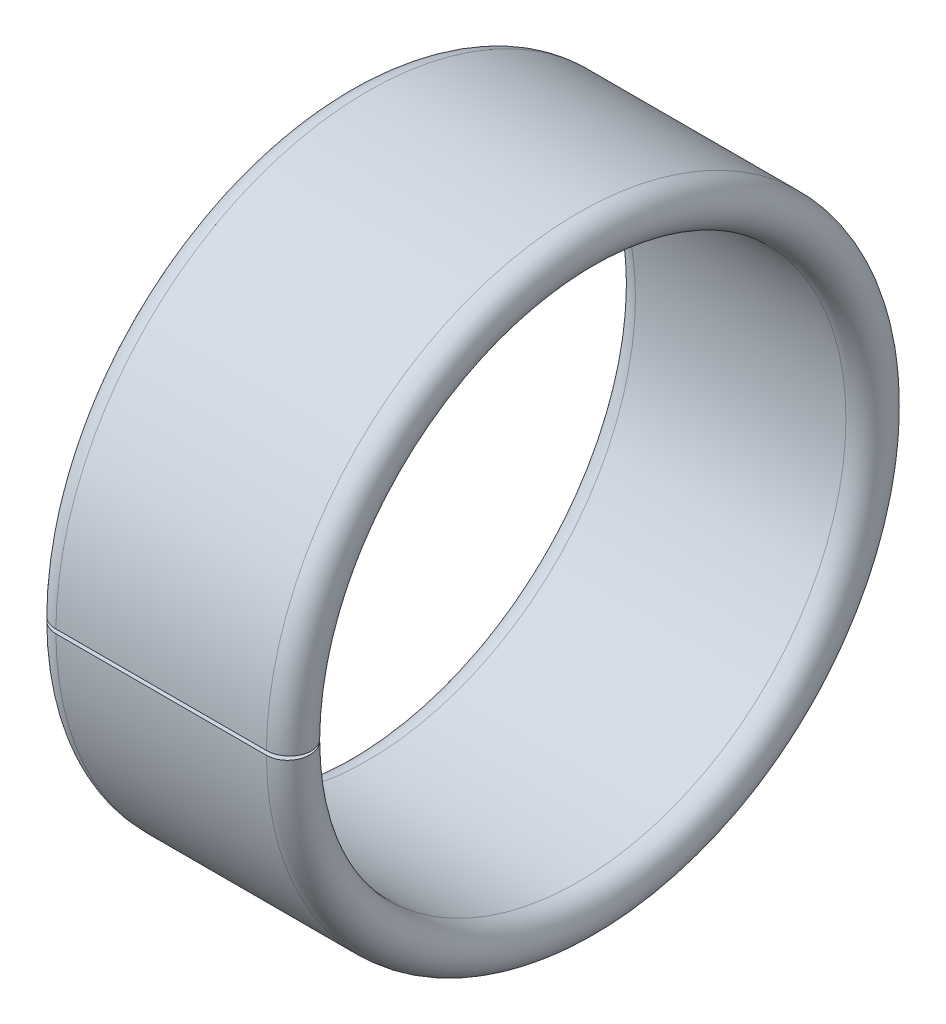
SolidWorks part; units mm, degrees
ref_plane "Front Plane" through (0, 0, 0) normal (0, 0, 1) x (1, 0, 0)
ref_plane "Top Plane" through (0, 0, 0) normal (0, 1, 0) x (1, 0, 0)
ref_plane "Right Plane" through (0, 0, 0) normal (1, 0, 0) x (0, 0, -1)
sketch "Sketch1" plane through (0, 0, 0) normal (0, 0, 1) x (1, 0, 0)
  line L0 (0.425, 5.15) -> (4.475, 5.15)
  line L1 (4.475, 6) -> (0.425, 6)
  line L2 (4.9, 0) -> (0, 0) construction
  arc A0 (0.425, 6) -> (0.425, 5.15) centre (0.425, 5.575) ccw
  arc A1 (4.475, 5.15) -> (4.475, 6) centre (4.475, 5.575) ccw
revolve "Revolve1" add sketch "Sketch1" angle 360 about L2
ref_plane "Plane1" through (4.9, 0, 0) normal (1, 0, 0) x (0, 0, -1)
sketch "Sketch2" plane through (0, 0, 0) normal (1, 0, 0) x (0, 0, -1)
  line L0 (-6.9996, -0.0746) -> (-4.8636, 0)
  line L1 (-4.8636, 0) -> (-6.9996, 0.0746)
  arc A0 (-6.9996, 0.0746) -> (-6.9996, -0.0746) centre (0, 0) ccw
extrude "Cut-Extrude1" cut sketch "Sketch2" along normal blind 4.9
ref_plane "ANBAU XY" through (0, 0, 0) normal (1, 0, 0) x (0, 0, -1)
ref_plane "ANBAU XZ" through (0, 0, 0) normal (0, -1, 0) x (-1, 0, 0)
ref_plane "ANBAU YZ" through (0, 0, 0) normal (0, 0, -1) x (-1, 0, 0)
ref_axis "ANBAU X" through (0, 0, 80.9) along (0, 0, -1)
ref_axis "ANBAU Y" through (0, -50, 0) along (0, 1, 0)
ref_axis "ANBAU Z" through (80.9, 0, 0) along (-1, 0, 0)
sketch3d "ANBAU"
  point P0 (0, 0, 0)
ref_plane "insert XY" through (0, 0, 0) normal (1, 0, 0) x (0, 0, -1)
ref_plane "insert XZ" through (0, 0, 0) normal (0, -1, 0) x (-1, 0, 0)
ref_plane "insert YZ" through (0, 0, 0) normal (0, 0, -1) x (-1, 0, 0)
ref_axis "insert X" through (0, 0, 80.9) along (0, 0, -1)
ref_axis "insert Y" through (0, -50, 0) along (0, 1, 0)
ref_axis "insert Z" through (80.9, 0, 0) along (-1, 0, 0)
sketch3d "insert"
  point P0 (0, 0, 0)
ref_plane "schraube_punkt XY" through (4.9, 0, 0) normal (1, 0, 0) x (0, 0, -1)
ref_plane "schraube_punkt XZ" through (0, 0, 0) normal (0, -1, 0) x (-1, 0, 0)
ref_plane "schraube_punkt YZ" through (0, 0, 0) normal (0, 0, -1) x (-1, 0, 0)
ref_axis "schraube_punkt X" through (4.9, 0, 80.9) along (0, 0, -1)
ref_axis "schraube_punkt Y" through (4.9, -50, 0) along (0, 1, 0)
ref_axis "schraube_punkt Z" through (80.9, 0, 0) along (-1, 0, 0)
sketch3d "schraube_punkt"
  point P0 (4.9, 0, 0)
other "Freeze***"
